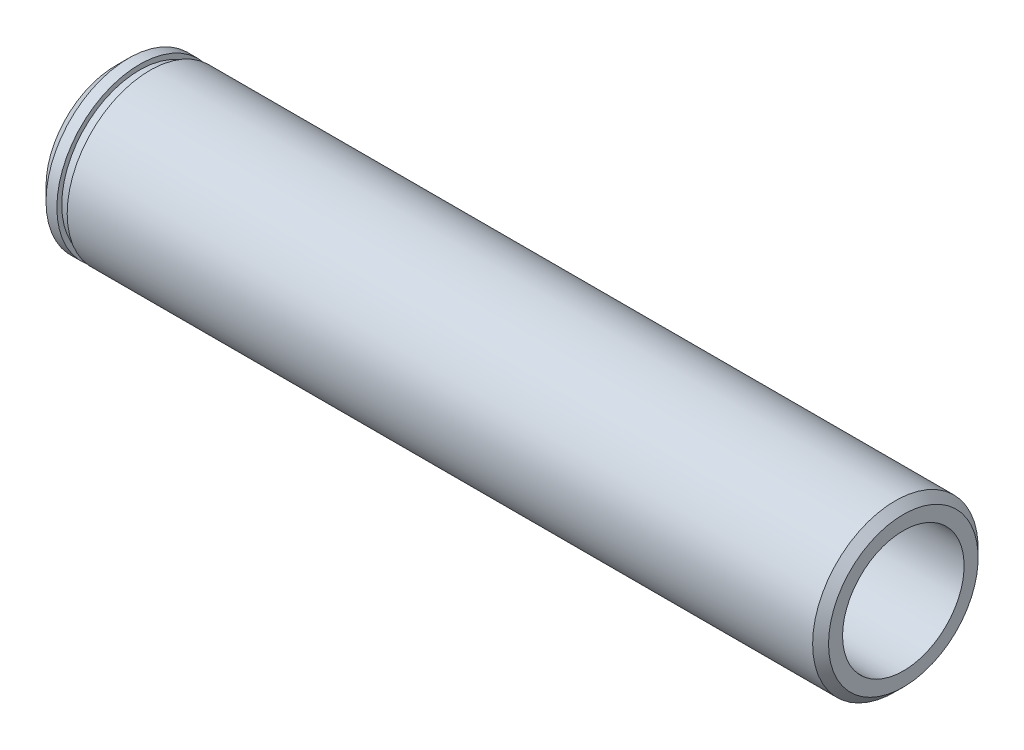
SolidWorks part; units mm, degrees
ref_plane "Front" through (0, 0, 0) normal (0, 0, 1) x (1, 0, 0)
ref_plane "Top" through (0, 0, 0) normal (0, 1, 0) x (1, 0, 0)
ref_plane "Right" through (0, 0, 0) normal (1, 0, 0) x (0, 0, -1)
ref_plane "Plane1" through (0, 0, 0) normal (0, 0, -1) x (-1, 0, 0)
sketch "Sketch1" plane through (0, 0, 0) normal (0, 0, -1) x (-1, 0, 0)
  line L0 (0, 5.9944) -> (0, 6.6675)
  line L1 (0, 6.6675) -> (-1.27, 7.9375)
  line L2 (-1.27, 7.9375) -> (-2.3114, 7.9375)
  line L3 (-2.3114, 7.9375) -> (-2.3114, 7.4676)
  line L4 (-2.3114, 7.4676) -> (-3.302, 7.4676)
  line L5 (-3.302, 7.4676) -> (-3.302, 7.9375)
  line L6 (-3.302, 7.9375) -> (-74.803, 7.9375)
  line L7 (-74.803, 7.9375) -> (-75.565, 7.1755)
  line L8 (-75.565, 7.1755) -> (-75.565, 5.8293)
  line L9 (-75.565, 5.8293) -> (-8.89, 5.8293)
  line L10 (-8.89, 5.8293) -> (-8.89, 5.9944)
  line L11 (-8.89, 5.9944) -> (0, 5.9944)
  line L12 (-75.565, 0) -> (0, 0) construction
revolve "Revolve1" add sketch "Sketch1" angle 360 about L12 reverse direction yes
